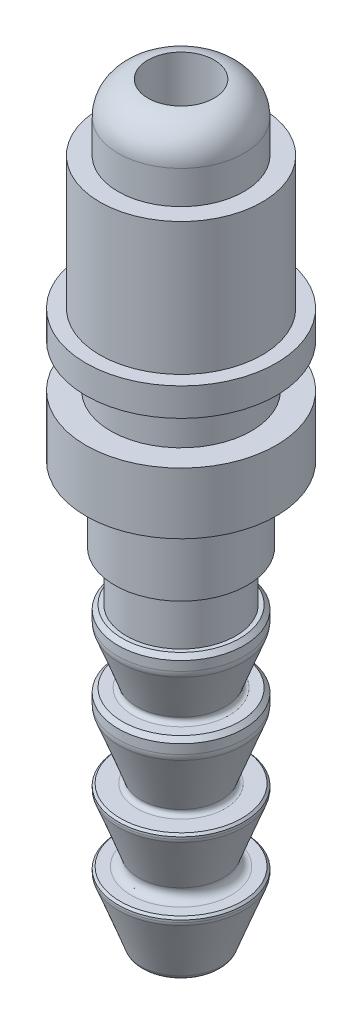
SolidWorks part; units mm, degrees
ref_plane "Front Plane" through (0, 0, 0) normal (0, 0, 1) x (1, 0, 0)
ref_plane "Top Plane" through (0, 0, 0) normal (0, 1, 0) x (1, 0, 0)
ref_plane "Right Plane" through (0, 0, 0) normal (1, 0, 0) x (0, 0, -1)
sketch "Sketch1" plane through (0, 0, 0) normal (0, 1, 0) x (1, 0, 0)
  circle A0 centre (0, 0) radius 5.75
  dimension "D1" = 11.5
extrude "Boss-Extrude1" add sketch "Sketch1" along normal blind 16
sketch "Sketch2" plane through (0, 16, 0) normal (0, 1, 0) x (1, 0, 0)
  circle A0 centre (0, 0) radius 4.9
  dimension "D1" = 9.8
extrude "Cut-Extrude1" cut sketch "Sketch2" against normal blind 8 flip side to cut
sketch "Sketch3" plane through (0, 16, 0) normal (0, 1, 0) x (1, 0, 0)
  circle A0 centre (0, 0) radius 3.8
  dimension "D1" = 7.6
extrude "Boss-Extrude2" add sketch "Sketch3" along normal blind 4
fillet "Fillet2" radius 2 1 edges at (0, 20, 3.8)
sketch "Sketch4" plane through (0, 0, 0) normal (0, -1, 0) x (1, 0, 0)
  circle A0 centre (0, 0) radius 4
  dimension "D1" = 8
extrude "Boss-Extrude3" add sketch "Sketch4" along normal blind 4.5
sketch "Sketch5" plane through (0, -4.5, 0) normal (0, -1, 0) x (1, 0, 0)
  circle A0 centre (0, 0) radius 3.3
  dimension "D1" = 6.6
extrude "Boss-Extrude4" add sketch "Sketch5" along normal blind 3
sketch "Sketch6" plane through (0, -7.5, 0) normal (0, -1, 0) x (1, 0, 0)
  circle A0 centre (0, 0) radius 3.8
  dimension "D1" = 7.6
extrude "Boss-Extrude5" add sketch "Sketch6" along normal blind 1
ref_plane "Plane1" through (0, -12.5, 0) normal (0, -1, 0) x (-1, 0, 0)
sketch "Sketch7" plane through (0, -12.5, 0) normal (0, -1, 0) x (-1, 0, 0)
  circle A0 centre (0, 0) radius 3.05
  dimension "D1" = 6.1
ref_axis "Axis1" through (0, 8, 0) along (0, -1, 0)
sketch "Sketch10" plane through (0, -12.5, 0) normal (0, -1, 0) x (-1, 0, 0)
  circle A0 centre (0, 0) radius 3.8 construction
  circle A1 centre (0, 0) radius 3.8
extrude "Boss-Extrude6" add sketch "Sketch10" against normal up to next
sketch "Sketch11" plane through (0, 0, 0) normal (0, 0, 1) x (1, 0, 0)
  line L0 (-2.3, -12.5) -> (-3.8, -8.5)
  line L1 (-3.05, -12.5) -> (3.05, -12.5) construction
  line L2 (-55, -12.5) -> (55, -12.5) construction
  line L3 (-3.8, -7.5) -> (-3.8, -12.5) construction
  line L4 (-3.8, -8.5) -> (-3.8, -12.5)
  line L5 (-3.8, -12.5) -> (-2.3, -12.5)
  line L6 (3.8, -7.5) -> (-3.8, -7.5) construction
  point P2 (0, 0)
  point P3 (-5.3, -12.5)
  point P11 (4.4174, -12.5)
  point P12 (-8.8832, -12.5)
  point P13 (0, 0)
  point P14 (-2.2637, -12.5)
  point P15 (0, 0)
  point P16 (0, 0)
  dimension "D1" = 1
  dimension "D2" = 1.5
revolve "Cut-Revolve1" cut sketch "Sketch11" angle 360 about axis through (0, 8, 0) along (0, -1, 0)
pattern_linear "LPattern1" count 4 spacing 4.35 along (0, -1, 0) of "Cut-Revolve1", "Boss-Extrude6", "Boss-Extrude5"
chamfer "Chamfer1" distance 0.25 angle 45 1 edges at (0, -7.5, -3.8)
chamfer "Chamfer2" distance 0.25 angle 45 1 edges at (0, -11.85, -3.8)
chamfer "Chamfer3" distance 0.125 angle 45 1 edges at (0, -16.85, 3.8)
chamfer "Chamfer4" distance 0.125 angle 45 1 edges at (0, -21.2, 3.8)
fillet "Fillet3" radius 0.5 2 edges at (0, -17.2, 3.8) (0, -21.55, 3.8)
fillet "Fillet4" radius 1 2 edges at (0, -12.85, 3.8) (0, -8.5, 3.8)
fillet "Fillet5" radius 0.25 2 edges at (0, -16.85, 2.3) (0, -11.85, -2.5437)
fillet "Fillet6" radius 0.5 1 edges at (0, -21.2, 2.3)
fillet "Fillet7" radius 0.5 1 edges at (0, -25.55, 2.3)
sketch "Sketch12" plane through (0, 0, 0) normal (1, 0, 0) x (0, 0, -1)
  line L0 (-5.75, 6.3) -> (-4.25, 6.3)
  line L1 (-5.75, 8) -> (-5.75, 0) construction
  line L2 (-4.25, 6.3) -> (-4.25, 3.7)
  line L3 (-4.25, 3.7) -> (-5.75, 3.7)
  line L4 (-5.75, 8) -> (-5.75, 0) construction
  line L5 (-5.75, 3.7) -> (-5.75, 6.3)
  line L6 (5.75, 8) -> (-5.75, 8) construction
  dimension "D1" = 2.6
  dimension "D2" = 1.7
  dimension "D3" = 1.5
revolve "Cut-Revolve2" cut sketch "Sketch12" angle 360 about axis through (0, 8, 0) along (0, -1, 0)
sketch "Sketch13" plane through (0, -25.55, 0) normal (0, -1, 0) x (1, 0, 0)
  circle A0 centre (0, 0) radius 2
  dimension "D1" = 4
extrude "Cut-Extrude2" cut sketch "Sketch13" against normal through all
